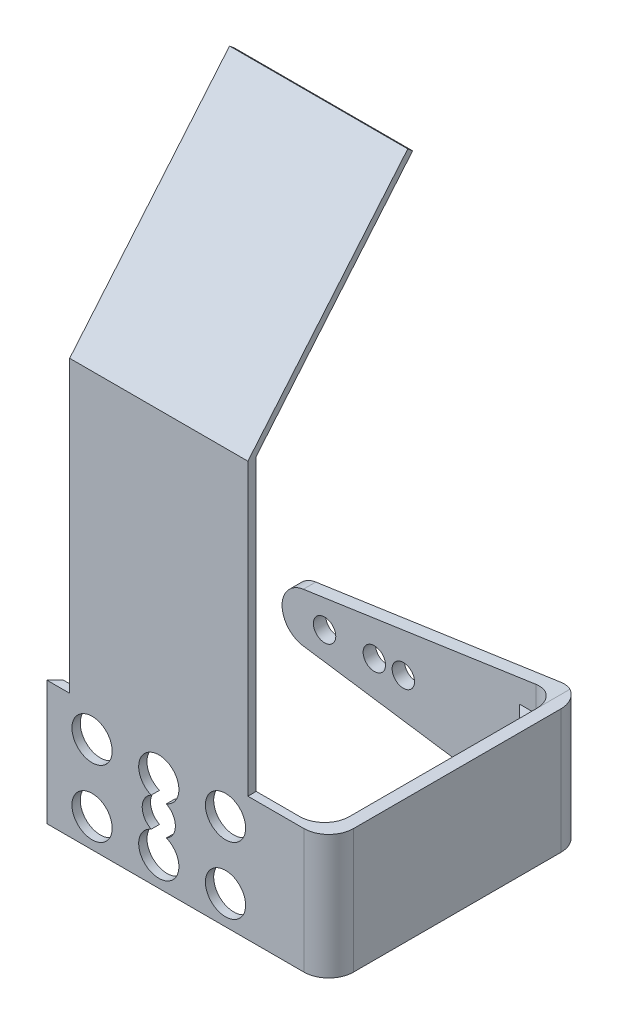
SolidWorks part; units mm, degrees
ref_plane "前视基准面" through (0, 0, 0) normal (0, 0, 1) x (1, 0, 0)
ref_plane "上视基准面" through (0, 0, 0) normal (0, 1, 0) x (1, 0, 0)
ref_plane "右视基准面" through (0, 0, 0) normal (1, 0, 0) x (0, 0, -1)
sketch "草图1" plane through (0, 0, 0) normal (0, 0, 1) x (1, 0, 0)
  line L1 (-13.5, -7.5) -> (13.5, -7.5)
  line L2 (-13.5, -7.5) -> (-13.5, 7.5)
  line L3 (-13.5, 7.5) -> (13.5, 7.5)
  line L4 (13.5, -7.5) -> (13.5, 7.5)
  line L5 (-13.5, -7.5) -> (13.5, 7.5) construction
  line L6 (-13.5, 7.5) -> (13.5, -7.5) construction
  point P0 (0, 0)
  dimension "D1" = 27
  dimension "D2" = 15
extrude "凸台-拉伸1" add sketch "草图1" along normal blind 1
sketch "草图2" plane through (0, 0, 1) normal (0, 0, 1) x (1, 0, 0)
  line L0 (-8.05, 4.025) -> (8.05, 4.025) construction
  line L3 (0, 1.6) -> (0, -1.6) construction
  line L4 (8.05, 4.025) -> (8.05, -4.025) construction
  line L5 (8.05, -4.025) -> (-8.05, -4.025) construction
  line L6 (-8.05, -4.025) -> (-8.05, 4.025) construction
  circle A0 centre (0, 4.025) radius 2.425
  circle A1 centre (0, -4.025) radius 2.425
  circle A2 centre (8.05, 4.025) radius 2.425
  circle A3 centre (8.05, -4.025) radius 2.425
  circle A4 centre (-8.05, 4.025) radius 2.425
  circle A5 centre (-8.05, -4.025) radius 2.425
  point P2 (0, 1.6)
  point P5 (0, -1.6)
  point P6 (0, 0)
  point P11 (-2.425, 4.025)
  point P20 (-5.625, 4.025)
  dimension "D1" = 4.85
  dimension "D4" = 3.2
  dimension "D2" = 3.2
extrude "切除-拉伸1" cut sketch "草图2" against normal through all
sketch "草图3" plane through (0, -7.5, 0) normal (0, -1, 0) x (1, 0, 0)
  line L0 (13.5, 0) -> (19, 0)
  line L1 (13.5, 1) -> (13.5, 0)
  line L2 (20.5, 1) -> (13.5, 1)
  line L3 (20.5, 1) -> (20.5, -30)
  line L5 (19, -28.5) -> (19, 0)
  line L6 (-4.5, -28.5) -> (-4.5, -30)
  line L7 (-4.5, -30) -> (20.5, -30)
  line L9 (-4.5, -28.5) -> (19, -28.5)
  dimension "D1" = 7
  dimension "D2" = 1.5
  dimension "D3" = 1.5
  dimension "D4" = 30
  dimension "D5" = 25
extrude "凸台-拉伸2" add sketch "草图3" against normal up to surface (15 mm away) up to face at (0, 7.5, 0.5)
sketch "草图6" plane through (0, 0, 0) normal (0, 1, 0) x (1, 0, 0)
  line L0 (19, 0) -> (19, 5)
  line L1 (19, 28.5) -> (19, 0) construction
  line L2 (19, 5) -> (14, 0)
  line L3 (19, 0) -> (-13.5, 0) construction
  line L4 (14, 0) -> (19, 0)
  line L5 (19, 28.5) -> (14, 28.5)
  line L6 (-4.5, 28.5) -> (19, 28.5) construction
  line L7 (14, 28.5) -> (19, 23.5)
  line L8 (19, 23.5) -> (19, 28.5)
  line L9 (20.5, 30) -> (-4.5, 30) construction
  line L10 (19, 19) -> (17.5, 19)
  line L11 (19, 19) -> (19, 21)
  line L12 (19, 21) -> (17.5, 21)
  line L13 (17.5, 19) -> (17.5, 21)
  point P18 (17.5, 20)
  dimension "D1" = 5
  dimension "D2" = 5
  dimension "D3" = 5
  dimension "D4" = 5
  dimension "D5" = 10
  dimension "D6" = 1.5
  dimension "D7" = 2
extrude "凸台-拉伸3" add sketch "草图6" along normal mid plane 8
sketch "草图7" plane through (0, 0, -30) normal (0, 0, -1) x (-1, 0, 0)
  circle A0 centre (0, 0) radius 1.35
chamfer "倒角1" distance 1 angle 45 1 edges at (-13.5, 0, 0)
sketch "草图8" plane through (0, 0, 0) normal (0, 0, -1) x (-1, 0, 0)
  circle A0 centre (0, 0) radius 2
  dimension "D1" = 4
extrude "切除-拉伸4" cut sketch "草图8" against normal up to next
sketch "草图9" plane through (0, 0, 1) normal (0, 0, 1) x (1, 0, 0)
  line L0 (0, 0) -> (0, 32.1698) construction
  line L1 (20.5, 7.5) -> (-13.5, 7.5) construction
  line L2 (10.75, 42.5) -> (-10.75, 42.5)
  line L3 (10.75, 42.5) -> (10.75, 7.5)
  line L4 (10.75, 7.5) -> (-10.75, 7.5)
  line L5 (-10.75, 42.5) -> (-10.75, 7.5)
  line L6 (10.75, 42.5) -> (-10.75, 7.5) construction
  line L7 (10.75, 7.5) -> (-10.75, 42.5) construction
  point P3 (0, 25)
  dimension "D1" = 35
  dimension "D2" = 21.5
extrude "凸台-拉伸4" add sketch "草图9" against normal up to surface (1 mm away) up to face at (0, 0, 0)
ref_plane "基准面1" through (0, 18.0524, 21.514) normal (0, 0.6428, 0.766) x (-1, 0, 0)
extrude "切除-拉伸5" cut sketch "草图7" against normal blind 10
sketch "草图12" plane through (0, 0, -30) normal (0, 0, -1) x (-1, 0, 0)
  line L1 (4.5, 7.5) -> (17, 7.5)
  line L2 (4.5, 7.5) -> (4.5, -7.5)
  line L3 (4.5, -7.5) -> (17, -7.5)
  line L4 (17, 7.5) -> (17, -7.5)
  dimension "D1" = 12.5
extrude "凸台-拉伸5" add sketch "草图12" against normal up to surface (1.5 mm away) up to face at (1.35, 0, -28.5)
sketch "草图13" plane through (0, 0, -30) normal (0, 0, -1) x (-1, 0, 0)
  circle A0 centre (3.5, 0) radius 1.35
  circle A1 centre (9.5, 0) radius 1.35
  dimension "D3" = 2.7
  dimension "D1" = 3.5
  dimension "D2" = 6
extrude "切除-拉伸6" cut sketch "草图13" against normal blind 10
sketch "草图14" plane through (0, 0, -30) normal (0, 0, -1) x (-1, 0, 0)
  line L0 (-19, 7.5) -> (12.0611, 2.9686)
  line L1 (-20.5, 7.5) -> (17, 7.5) construction
  line L2 (11.9416, -2.9836) -> (-19, -7.5)
  line L3 (17, -7.5) -> (-20.5, -7.5) construction
  line L4 (-19, -7.5) -> (17, -7.5)
  line L5 (17, -7.5) -> (17, 7.5)
  line L6 (17, 7.5) -> (-19, 7.5)
  line L7 (-1000, 0) -> (49000, 0) construction
  line L8 (-20.5, 7.5) -> (-20.5, -7.5) construction
  arc A0 (12.0611, 2.9686) -> (11.9416, -2.9836) centre (11.628, 0) cw
  dimension "D2" = 3
  dimension "D1" = 1.5
extrude "切除-拉伸7" cut sketch "草图14" against normal blind 10
fillet "圆角1" radius 3 6 edges at (20.5, 0, -30) (20.5, 0, 1) (19, 5.75, 0) (19, -5.75, 0) (19, 5.75, -28.5) (19, -5.75, -28.5)
sketch "草图16" plane through (0, 18.0524, 21.514) normal (0, 0.6428, 0.766) x (-1, 0, 0)
  line L0 (-10.75, -5.1025) -> (-10.75, -31.9141) construction
  line L1 (10.75, -31.9141) -> (-10.75, -31.9141)
  line L2 (10.75, -31.9141) -> (10.75, -61.9141)
  line L3 (10.75, -61.9141) -> (-10.75, -61.9141)
  line L4 (-10.75, -31.9141) -> (-10.75, -61.9141)
  dimension "D1" = 30
extrude "凸台-拉伸6" add sketch "草图16" against normal up to vertex (0.766 mm away) up to point (10.75, 42.5, 0)
